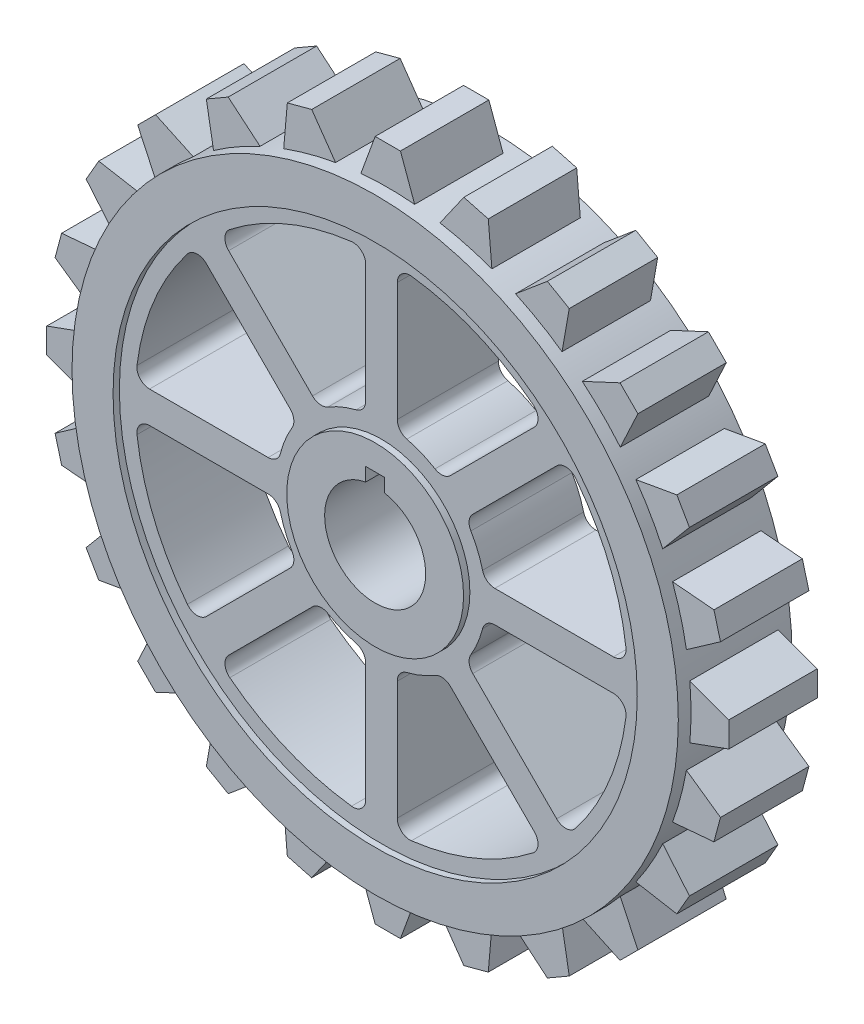
SolidWorks part; units mm, degrees
ref_plane "Front Plane" through (0, 0, 0) normal (0, 0, 1) x (1, 0, 0)
ref_plane "Top Plane" through (0, 0, 0) normal (0, 1, 0) x (1, 0, 0)
ref_plane "Right Plane" through (0, 0, 0) normal (1, 0, 0) x (0, 0, -1)
sketch "Sketch1" plane through (0, 0, 0) normal (0, 0, 1) x (1, 0, 0)
  line L0 (-1.5, 10) -> (1.5, 10)
  line L1 (1.5, 10) -> (1.5, 7.8581)
  line L2 (-1.5, 10) -> (-1.5, 7.8581)
  line L3 (0, -55) -> (0, 55) construction
  line L4 (0, -964.1974) -> (0, 49035.8026) construction
  line L5 (-2, 54) -> (2, 54)
  line L6 (-2, 54) -> (-4.2525, 47.8113)
  line L7 (2, 54) -> (4.2525, 47.8113)
  line L8 (15.9081, 51.6424) -> (16.4821, 45.0815)
  line L9 (12.0444, 52.6776) -> (15.9081, 51.6424)
  line L10 (12.0444, 52.6776) -> (8.2668, 47.2828)
  line L11 (28.7321, 45.7654) -> (27.5884, 39.2795)
  line L12 (25.2679, 47.7654) -> (28.7321, 45.7654)
  line L13 (25.2679, 47.7654) -> (20.2228, 43.532)
  line L14 (39.598, 36.7696) -> (36.8146, 30.8007)
  line L15 (36.7696, 39.598) -> (39.598, 36.7696)
  line L16 (36.7696, 39.598) -> (30.8007, 36.8146)
  line L17 (47.7654, 25.2679) -> (43.532, 20.2228)
  line L18 (45.7654, 28.7321) -> (47.7654, 25.2679)
  line L19 (45.7654, 28.7321) -> (39.2795, 27.5884)
  line L20 (52.6776, 12.0444) -> (47.2828, 8.2668)
  line L21 (51.6424, 15.9081) -> (52.6776, 12.0444)
  line L22 (51.6424, 15.9081) -> (45.0815, 16.4821)
  line L23 (54, -2) -> (47.8113, -4.2525)
  line L24 (54, 2) -> (54, -2)
  line L25 (54, 2) -> (47.8113, 4.2525)
  line L26 (51.6424, -15.9081) -> (45.0815, -16.4821)
  line L27 (52.6776, -12.0444) -> (51.6424, -15.9081)
  line L28 (52.6776, -12.0444) -> (47.2828, -8.2668)
  line L29 (45.7654, -28.7321) -> (39.2795, -27.5884)
  line L30 (47.7654, -25.2679) -> (45.7654, -28.7321)
  line L31 (47.7654, -25.2679) -> (43.532, -20.2228)
  line L32 (36.7696, -39.598) -> (30.8007, -36.8146)
  line L33 (39.598, -36.7696) -> (36.7696, -39.598)
  line L34 (39.598, -36.7696) -> (36.8146, -30.8007)
  line L35 (25.2679, -47.7654) -> (20.2228, -43.532)
  line L36 (28.7321, -45.7654) -> (25.2679, -47.7654)
  line L37 (28.7321, -45.7654) -> (27.5884, -39.2795)
  line L38 (12.0444, -52.6776) -> (8.2668, -47.2828)
  line L39 (15.9081, -51.6424) -> (12.0444, -52.6776)
  line L40 (15.9081, -51.6424) -> (16.4821, -45.0815)
  line L41 (-2, -54) -> (-4.2525, -47.8113)
  line L42 (2, -54) -> (-2, -54)
  line L43 (2, -54) -> (4.2525, -47.8113)
  line L44 (-15.9081, -51.6424) -> (-16.4821, -45.0815)
  line L45 (-12.0444, -52.6776) -> (-15.9081, -51.6424)
  line L46 (-12.0444, -52.6776) -> (-8.2668, -47.2828)
  line L47 (-28.7321, -45.7654) -> (-27.5884, -39.2795)
  line L48 (-25.2679, -47.7654) -> (-28.7321, -45.7654)
  line L49 (-25.2679, -47.7654) -> (-20.2228, -43.532)
  line L50 (-39.598, -36.7696) -> (-36.8146, -30.8007)
  line L51 (-36.7696, -39.598) -> (-39.598, -36.7696)
  line L52 (-36.7696, -39.598) -> (-30.8007, -36.8146)
  line L53 (-47.7654, -25.2679) -> (-43.532, -20.2228)
  line L54 (-45.7654, -28.7321) -> (-47.7654, -25.2679)
  line L55 (-45.7654, -28.7321) -> (-39.2795, -27.5884)
  line L56 (-52.6776, -12.0444) -> (-47.2828, -8.2668)
  line L57 (-51.6424, -15.9081) -> (-52.6776, -12.0444)
  line L58 (-51.6424, -15.9081) -> (-45.0815, -16.4821)
  line L59 (-54, 2) -> (-47.8113, 4.2525)
  line L60 (-54, -2) -> (-54, 2)
  line L61 (-54, -2) -> (-47.8113, -4.2525)
  line L62 (-51.6424, 15.9081) -> (-45.0815, 16.4821)
  line L63 (-52.6776, 12.0444) -> (-51.6424, 15.9081)
  line L64 (-52.6776, 12.0444) -> (-47.2828, 8.2668)
  line L65 (-45.7654, 28.7321) -> (-39.2795, 27.5884)
  line L66 (-47.7654, 25.2679) -> (-45.7654, 28.7321)
  line L67 (-47.7654, 25.2679) -> (-43.532, 20.2228)
  line L68 (-36.7696, 39.598) -> (-30.8007, 36.8146)
  line L69 (-39.598, 36.7696) -> (-36.7696, 39.598)
  line L70 (-39.598, 36.7696) -> (-36.8146, 30.8007)
  line L71 (-25.2679, 47.7654) -> (-20.2228, 43.532)
  line L72 (-28.7321, 45.7654) -> (-25.2679, 47.7654)
  line L73 (-28.7321, 45.7654) -> (-27.5884, 39.2795)
  line L74 (-12.0444, 52.6776) -> (-8.2668, 47.2828)
  line L75 (-15.9081, 51.6424) -> (-12.0444, 52.6776)
  line L76 (-15.9081, 51.6424) -> (-16.4821, 45.0815)
  line L77 (2.5, 36.7253) -> (2.5, 17.9444)
  line L80 (0, 0) -> (27.5772, 27.5772) construction
  line L81 (24.201, 27.7365) -> (10.9208, 14.4563)
  line L83 (27.7365, 24.201) -> (14.4563, 10.9208)
  line L84 (36.7253, 2.5) -> (17.9444, 2.5)
  line L85 (36.7253, -2.5) -> (17.9444, -2.5)
  line L86 (27.7365, -24.201) -> (14.4563, -10.9208)
  line L87 (24.201, -27.7365) -> (10.9208, -14.4563)
  line L88 (2.5, -36.7253) -> (2.5, -17.9444)
  line L89 (-2.5, -36.7253) -> (-2.5, -17.9444)
  line L90 (-24.201, -27.7365) -> (-10.9208, -14.4563)
  line L91 (-27.7365, -24.201) -> (-14.4563, -10.9208)
  line L92 (-36.7253, -2.5) -> (-17.9444, -2.5)
  line L93 (-36.7253, 2.5) -> (-17.9444, 2.5)
  line L94 (-27.7365, 24.201) -> (-14.4563, 10.9208)
  line L95 (-24.201, 27.7365) -> (-10.9208, 14.4563)
  line L96 (-2.5, 36.7253) -> (-2.5, 17.9444)
  arc A0 (-1.5, 7.8581) -> (1.5, 7.8581) centre (0, 0) ccw
  circle A1 centre (0, 0) radius 14
  circle A2 centre (0, 0) radius 48
  circle A3 centre (0, 0) radius 41.5
  arc A4 (4.0135, 16.0044) -> (8.4789, 14.1548) centre (0, 0) cw
  arc A5 (4.7432, 38.7105) -> (24.0185, 30.7264) centre (0, 0) cw
  arc A12 (10.9208, 14.4563) -> (8.4789, 14.1548) centre (9.5066, 15.8706) cw
  arc A13 (24.201, 27.7365) -> (24.0185, 30.7264) centre (22.7868, 29.1507) ccw
  arc A14 (2.5, 17.9444) -> (4.0135, 16.0044) centre (4.5, 17.9444) ccw
  arc A15 (2.5, 36.7253) -> (4.7432, 38.7105) centre (4.5, 36.7253) cw
  arc A16 (27.7365, 24.201) -> (30.7264, 24.0185) centre (29.1507, 22.7868) cw
  arc A17 (14.4563, 10.9208) -> (14.1548, 8.4789) centre (15.8706, 9.5066) ccw
  arc A18 (14.1548, 8.4789) -> (16.0044, 4.0135) centre (0, 0) cw
  arc A19 (17.9444, 2.5) -> (16.0044, 4.0135) centre (17.9444, 4.5) cw
  arc A20 (36.7253, 2.5) -> (38.7105, 4.7432) centre (36.7253, 4.5) ccw
  arc A21 (30.7264, 24.0185) -> (38.7105, 4.7432) centre (0, 0) cw
  arc A22 (36.7253, -2.5) -> (38.7105, -4.7432) centre (36.7253, -4.5) cw
  arc A23 (17.9444, -2.5) -> (16.0044, -4.0135) centre (17.9444, -4.5) ccw
  arc A24 (16.0044, -4.0135) -> (14.1548, -8.4789) centre (0, 0) cw
  arc A25 (14.4563, -10.9208) -> (14.1548, -8.4789) centre (15.8706, -9.5066) cw
  arc A26 (27.7365, -24.201) -> (30.7264, -24.0185) centre (29.1507, -22.7868) ccw
  arc A27 (38.7105, -4.7432) -> (30.7264, -24.0185) centre (0, 0) cw
  arc A28 (24.201, -27.7365) -> (24.0185, -30.7264) centre (22.7868, -29.1507) cw
  arc A29 (10.9208, -14.4563) -> (8.4789, -14.1548) centre (9.5066, -15.8706) ccw
  arc A30 (8.4789, -14.1548) -> (4.0135, -16.0044) centre (0, 0) cw
  arc A31 (2.5, -17.9444) -> (4.0135, -16.0044) centre (4.5, -17.9444) cw
  arc A32 (2.5, -36.7253) -> (4.7432, -38.7105) centre (4.5, -36.7253) ccw
  arc A33 (24.0185, -30.7264) -> (4.7432, -38.7105) centre (0, 0) cw
  arc A34 (-2.5, -36.7253) -> (-4.7432, -38.7105) centre (-4.5, -36.7253) cw
  arc A35 (-2.5, -17.9444) -> (-4.0135, -16.0044) centre (-4.5, -17.9444) ccw
  arc A36 (-4.0135, -16.0044) -> (-8.4789, -14.1548) centre (0, 0) cw
  arc A37 (-10.9208, -14.4563) -> (-8.4789, -14.1548) centre (-9.5066, -15.8706) cw
  arc A38 (-24.201, -27.7365) -> (-24.0185, -30.7264) centre (-22.7868, -29.1507) ccw
  arc A39 (-4.7432, -38.7105) -> (-24.0185, -30.7264) centre (0, 0) cw
  arc A40 (-27.7365, -24.201) -> (-30.7264, -24.0185) centre (-29.1507, -22.7868) cw
  arc A41 (-14.4563, -10.9208) -> (-14.1548, -8.4789) centre (-15.8706, -9.5066) ccw
  arc A42 (-14.1548, -8.4789) -> (-16.0044, -4.0135) centre (0, 0) cw
  arc A43 (-17.9444, -2.5) -> (-16.0044, -4.0135) centre (-17.9444, -4.5) cw
  arc A44 (-36.7253, -2.5) -> (-38.7105, -4.7432) centre (-36.7253, -4.5) ccw
  arc A45 (-30.7264, -24.0185) -> (-38.7105, -4.7432) centre (0, 0) cw
  arc A46 (-36.7253, 2.5) -> (-38.7105, 4.7432) centre (-36.7253, 4.5) cw
  arc A47 (-17.9444, 2.5) -> (-16.0044, 4.0135) centre (-17.9444, 4.5) ccw
  arc A48 (-16.0044, 4.0135) -> (-14.1548, 8.4789) centre (0, 0) cw
  arc A49 (-14.4563, 10.9208) -> (-14.1548, 8.4789) centre (-15.8706, 9.5066) cw
  arc A50 (-27.7365, 24.201) -> (-30.7264, 24.0185) centre (-29.1507, 22.7868) ccw
  arc A51 (-38.7105, 4.7432) -> (-30.7264, 24.0185) centre (0, 0) cw
  arc A52 (-24.201, 27.7365) -> (-24.0185, 30.7264) centre (-22.7868, 29.1507) cw
  arc A53 (-10.9208, 14.4563) -> (-8.4789, 14.1548) centre (-9.5066, 15.8706) ccw
  arc A54 (-8.4789, 14.1548) -> (-4.0135, 16.0044) centre (0, 0) cw
  arc A55 (-2.5, 17.9444) -> (-4.0135, 16.0044) centre (-4.5, 17.9444) cw
  arc A56 (-2.5, 36.7253) -> (-4.7432, 38.7105) centre (-4.5, 36.7253) ccw
  arc A57 (-24.0185, 30.7264) -> (-4.7432, 38.7105) centre (0, 0) cw
  point P18 (0, 48)
  point P138 (0, 0)
  point P236 (0, 0)
  dimension "D1" = 16
  dimension "D5" = 28
  dimension "D10" = 6.5
  dimension "D13" = 96
  dimension "D16" = 2.5
  dimension "D17" = 2.5
  dimension "D15" = 2
  dimension "D2" = 3
  dimension "D3" = 10
  dimension "D4" = 1.5
  dimension "D6" = 40
  dimension "D7" = 4
  dimension "D8" = 2
  dimension "D9" = 6
  dimension "D11" = 24
  dimension "D12" = 108
  dimension "D14" = 2.5
  dimension "D18" = 8
  dimension "D19" = 2.5
extrude "Boss-Extrude1" add sketch "Sketch1" along normal mid plane 18 contours A1 A0 L2 L0 L1 region at (-13.604, 0, 0)
extrude "Boss-Extrude2" add sketch "Sketch1<3>" along normal mid plane 16 contours A3 A1 L77 A15 A5 A13 L81 A12 A4 A14 A16 A21 A20 L84 A19 A18 A17 L83 A22 A27 A26 L86 A25 A24 A23 L85 A28 A33 A32 L88 A31 A30 A29 L87 A34 A39 A38 L90 A37 A36 A35 L89 A40 A45 region at (-40.3262, 0, 0)
sketch "Sketch1<3>" plane through (0, 0, 0) normal (0, 0, 1) x (1, 0, 0) same geometry as "Sketch1"
extrude "Boss-Extrude3" add sketch "Sketch1<4>" along normal mid plane 18 contours A2 A3 region at (0, 46.6424, 0)
sketch "Sketch1<4>" plane through (0, 0, 0) normal (0, 0, 1) x (1, 0, 0) same geometry as "Sketch1"
extrude "Boss-Extrude4" add sketch "Sketch1<5>" along normal mid plane 14 contours A2 L7 L5 L6 | A2 L8 L9 L10 | A2 L11 L12 L13 | A2 L14 L15 L16 | A2 L17 L18 L19 | A2 L20 L21 L22 | A2 L23 L24 L25 | A2 L26 L27 L28 | A2 L29 L30 L31 | A2 L32 L33 L34 | A2 L35 L36 L37 | A2 L38 L39 L40 | A2 L41 L42 L43 | A2 L44 L45 L46 | A2 L47 L48 L49 | A2 L50 L51 L52 | A2 L53 L54 L55 | A2 L56 L57 L58 | A2 L59 L60 L61 | A2 L62 L63 L64 | A2 L65 L66 L67 | A2 L68 L69 L70 | A2 L71 L72 L73 | A2 L74 L75 L76 region at (0, 50.6094, 0) region at (-13.0987, 48.8849, 0) region at (13.0987, 48.8849, 0) region at (-25.3047, 43.829, 0) region at (25.3047, 43.829, 0) region at (-35.7862, 35.7862, 0) region at (35.7862, 35.7862, 0) region at (-43.829, 25.3047, 0) region at (43.829, 25.3047, 0) region at (-48.8849, 13.0987, 0) region at (48.8849, 13.0987, 0) region at (-50.6094, 0, 0) region at (50.6094, 0, 0) region at (-48.8849, -13.0987, 0) region at (48.8849, -13.0987, 0) region at (-43.829, -25.3047, 0) region at (43.829, -25.3047, 0) region at (-35.7862, -35.7862, 0) region at (35.7862, -35.7862, 0) region at (-25.3047, -43.829, 0) region at (25.3047, -43.829, 0) region at (-13.0987, -48.8849, 0) region at (13.0987, -48.8849, 0) region at (0, -50.6094, 0)
sketch "Sketch1<5>" plane through (0, 0, 0) normal (0, 0, 1) x (1, 0, 0) same geometry as "Sketch1"
